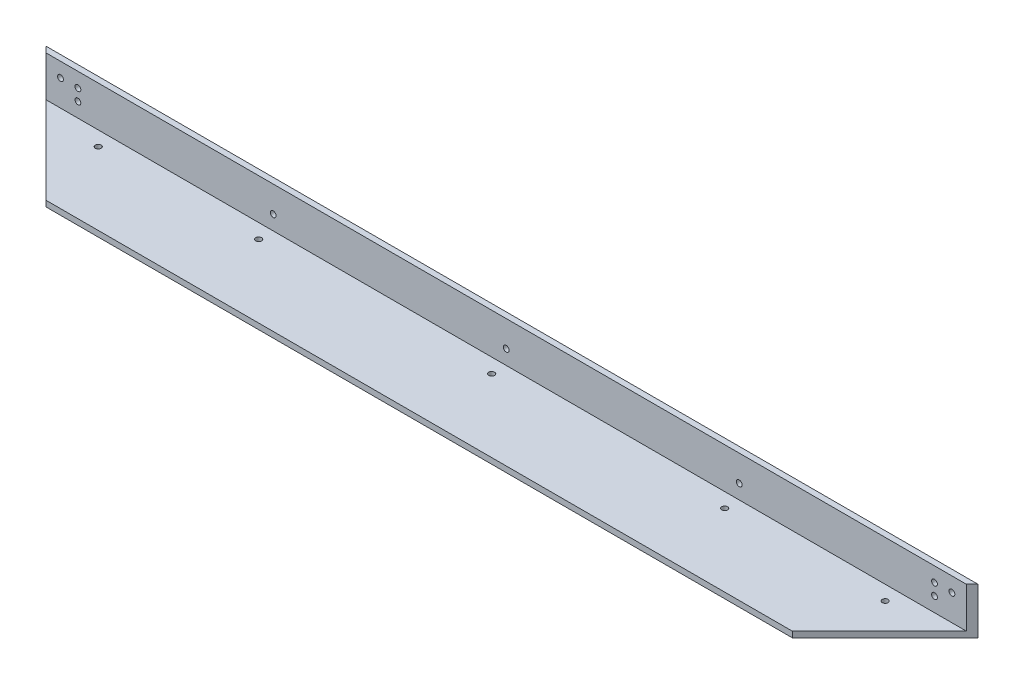
SolidWorks part; units mm, degrees
ref_plane "Front Plane" through (0, 0, 0) normal (0, 0, 1) x (1, 0, 0)
ref_plane "Top Plane" through (0, 0, 0) normal (0, 1, 0) x (1, 0, 0)
ref_plane "Right Plane" through (0, 0, 0) normal (1, 0, 0) x (0, 0, -1)
sketch "Sketch1" plane through (0, 0, 0) normal (1, 0, 0) x (0, 0, -1)
  line L0 (0, 0) -> (-50.8, 0)
  line L1 (-50.8, 0) -> (-50.8, 3.175)
  line L2 (-50.8, 3.175) -> (-3.175, 3.175)
  line L3 (-3.175, 3.175) -> (-3.175, 25.4)
  line L4 (-3.175, 25.4) -> (0, 25.4)
  line L5 (0, 25.4) -> (0, 0)
  dimension "LHeight" = 25.4
  dimension "LWidth" = 50.8
  dimension "LMaterialThickness" = 3.175
  dimension "D1" = 47.625
  dimension "D2" = 22.225
  dimension "D3" = 3.175
extrude "Boss-Extrude1" add sketch "Sketch1" along normal blind 510
chamfer "Chamfer6" distance 50.8 angle 45 1 edges at (510, 1.5875, 50.8)
chamfer "Chamfer7" distance 50.8 angle 45 1 edges at (0, 1.5875, 50.8)
sketch "BackSideHoles-Sketch2" plane through (0, 0, 0) normal (0, 0, -1) x (-1, 0, 0)
  line L0 (0, 0) -> (0, 25.4) construction
  line L1 (-510, 0) -> (0, 0) construction
  line L2 (-510, 0) -> (-510, 25.4) construction
  line L3 (-510, 25.4) -> (0, 25.4) construction
  circle A0 centre (-498.8875, 17.4625) radius 1.5875
  circle A1 centre (-489.3625, 17.4625) radius 1.5875
  circle A2 centre (-20.6375, 17.4625) radius 1.5875
  circle A4 centre (-11.1125, 17.4625) radius 1.5875
  circle A5 centre (-20.6375, 11.1125) radius 1.5875
  circle A6 centre (-489.3625, 11.1125) radius 1.5875
  circle A8 centre (-382.5, 11.1125) radius 1.5875
  circle A9 centre (-255, 11.1125) radius 1.5875
  circle A10 centre (-127.5, 11.1125) radius 1.5875
  dimension "D5" = 3.175
  dimension "D2" = 20.6375
  dimension "D4" = 20.6375
  dimension "D8" = 127.5
  dimension "D9" = 127.5
  dimension "D10" = 127.5
  dimension "D11" = 11.1125
  dimension "D6" = 7.9375
  dimension "D7" = 11.1125
  dimension "D3" = 11.1125
sketch "BottomHoles-Sketch3" plane through (0, 0, 0) normal (0, -1, 0) x (1, 0, 0)
  line L0 (510, 0) -> (0, 0) construction
  circle A7 centre (39.6875, 11.1125) radius 1.5875
  circle A8 centre (470.3125, 11.1125) radius 1.5875
  circle A9 centre (127.5, 11.1125) radius 1.5875
  circle A10 centre (255, 11.1125) radius 1.5875
  circle A11 centre (382.5, 11.1125) radius 1.5875
  dimension "D5" = 3.175
  dimension "D2" = 39.6875
  dimension "D3" = 39.6875
  dimension "D4" = 11.1125
  dimension "D1" = 127.5
  dimension "D6" = 127.5
  dimension "D7" = 127.5
extrude "BottomHoles-Cut-Extrude1" cut sketch "BottomHoles-Sketch3" against normal through all
extrude "BackSideHoles-Cut-Extrude2" cut sketch "BackSideHoles-Sketch2" against normal through all
equation "\"LowerRailWidth\"= 2.00in"
equation "\"LowerRailHeight\"= 1.00in"
equation "\"RailThickness\"= .125in'Spec"
equation "\"SideRailHoleX1FromSide\"= \"HoleOffsetFromSide\""
equation "\"SideRailHoleX2FromSide\"= \"VSWidth\" - \"HoleOffsetFromEdge\" - \"RailThickness\"'Equals 20.6375"
equation "\"SideRailHoleY1FromEdge\"= \"HoleOffsetFromEdge\""
equation "\"FrontBackRailLength\"= 510mm"
equation "\"VSWidth\"= 1.25in'Spec"
equation "\"HoleOffsetFromEdge\"= \"RailThickness\" * 2.5"
equation "\"HoleOffsetFromSide\"= \"RailThickness\" * 3.5"
equation "\"SideRailHoleY2FromSide\"= \"HoleOffsetFromSide\""
equation "\"FasteningHoleDiameter\"= .125in"
equation "\"D1@Boss-Extrude1\"=\"FrontBackRailLength\""
equation "\"D1@Chamfer6\"=\"LowerRailWidth\""
equation "\"D1@Chamfer7\"=\"LowerRailWidth\""
equation "\"D2@BackSideHoles-Sketch2\" = \"SideRailHoleX2FromSide\""
equation "\"D4@BackSideHoles-Sketch2\" = \"SideRailHoleX2FromSide\""
equation "\"D5@BackSideHoles-Sketch2\" = \"FasteningHoleDiameter\""
equation "\"LHeight@Sketch1\"=\"LowerRailHeight\""
equation "\"LWidth@Sketch1\"=\"LowerRailWidth\""
equation "\"24vPSUMountingHoleDistanceFromEdge\"= 33.5mm"
equation "\"24vPSUMountingHoleDistance\"= 150mm"
equation "\"24vPSUMountingHoleDiameter\"= 2.5mm"
equation "\"LowerCornerBlockWidth\"= \"LowerRailWidth\" - \"RailThickness\" * 2'Room for left front stepper"
equation "\"D2@BottomHoles-Sketch3\"=\"CornerEnclosureOffset\""
equation "\"D3@BottomHoles-Sketch3\"=\"CornerEnclosureOffset\""
equation "\"D4@BottomHoles-Sketch3\"=\"LowerCornerBlockY1FromSide\""
equation "\"D5@BottomHoles-Sketch3\"=\"FasteningHoleDiameter\""
equation "\"CornerEnclosureOffset\"= \"LowerCornerBlockWidth\" - \"HoleOffsetFromEdge\" + \"RailThickness\""
equation "\"LowerCornerBlockY1FromSide\"= \"HoleOffsetFromSide\""
equation "\"FrontOrBackEnclosureOffsets\"= \"FrontBackRailLength\" / 4"
equation "\"D1@BottomHoles-Sketch3\"=\"FrontOrBackEnclosureOffsets\""
equation "\"D6@BottomHoles-Sketch3\"=\"FrontOrBackEnclosureOffsets\""
equation "\"D7@BottomHoles-Sketch3\"=\"FrontOrBackEnclosureOffsets\""
equation "\"D8@BackSideHoles-Sketch2\"=\"FrontOrBackEnclosureOffsets\""
equation "\"D9@BackSideHoles-Sketch2\"=\"FrontOrBackEnclosureOffsets\""
equation "\"D10@BackSideHoles-Sketch2\"=\"FrontOrBackEnclosureOffsets\""
equation "\"D11@BackSideHoles-Sketch2\"=\"SideRailHoleX1FromSide\""
equation "\"D6@BackSideHoles-Sketch2\"=\"SideRailHoleY1FromEdge\""
equation "\"D7@BackSideHoles-Sketch2\"=\"SideRailHoleY2FromSide\""
equation "\"D3@BackSideHoles-Sketch2\"=\"SideRailHoleX1FromSide\""
